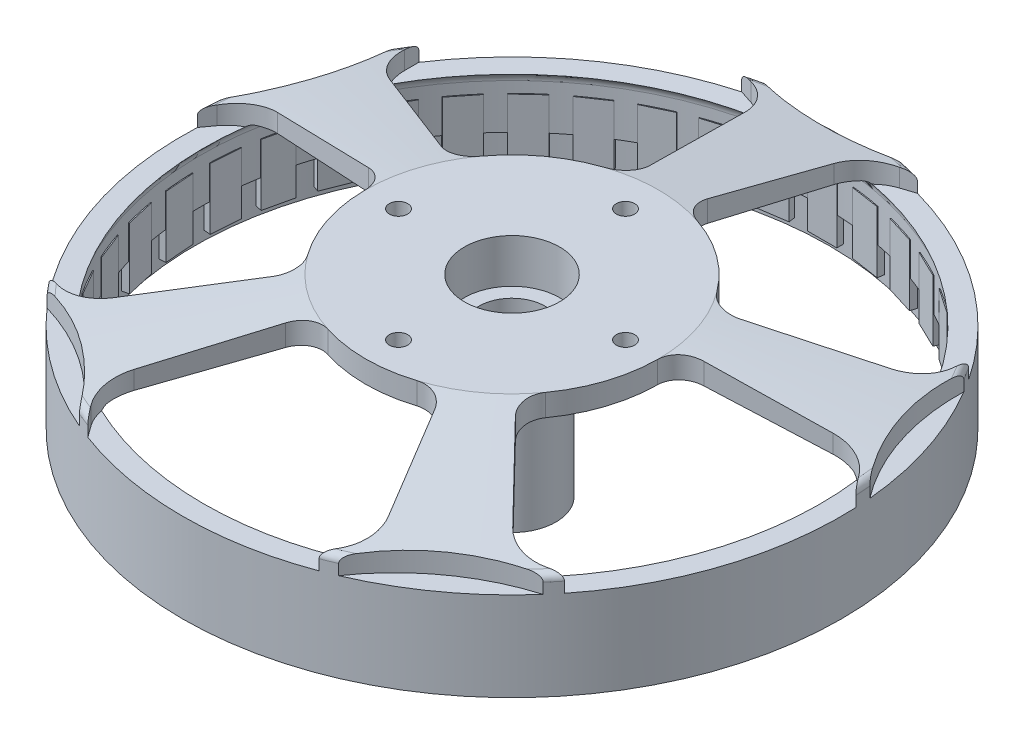
SolidWorks part; units mm, degrees
ref_plane "Front Plane" through (0, 0, 0) normal (0, 0, 1) x (1, 0, 0)
ref_plane "Top Plane" through (0, 0, 0) normal (0, 1, 0) x (1, 0, 0)
ref_plane "Right Plane" through (0, 0, 0) normal (1, 0, 0) x (0, 0, -1)
sketch "Sketch2" plane through (0, 0, 0) normal (0, 0, 1) x (1, 0, 0)
  line L0 (0, 0) -> (0, -18.25) construction
  line L1 (0, -18.25) -> (45, -18.25) construction
  line L2 (45, -18.25) -> (45, -6.1)
  line L3 (20, -3) -> (8.5, -3)
  line L4 (42.5, -5.8) -> (42.5, -13.25)
  line L5 (42.5, -13.25) -> (43.3, -13.25)
  line L6 (43.3, -13.25) -> (43.3, -18.25)
  line L7 (43.3, -18.25) -> (45, -18.25)
  line L8 (20, 0) -> (6.5, 0)
  line L9 (20, 0) -> (45, -3.8)
  line L10 (45, -3.8) -> (45, -6.1)
  line L12 (8.5, -3) -> (8.5, -8)
  line L13 (20, -3) -> (42.5, -5.8)
  line L14 (8.5, -8) -> (6, -8)
  line L15 (6, -8) -> (6, -26.3)
  line L16 (6, -26.3) -> (4, -26.3)
  line L17 (4, -26.3) -> (4, -19.5)
  line L18 (4, -19.5) -> (4.5, -19.5)
  line L19 (4.5, -19.5) -> (4.5, -6)
  line L20 (4.5, -6) -> (6.5, -6)
  line L21 (6.5, -6) -> (6.5, 0)
  dimension "D1" = 18.25
  dimension "D2" = 45
  dimension "D3" = 12.15
  dimension "D4" = 1.7
  dimension "D5" = 5
  dimension "D6" = 2.5
  dimension "D7" = 3
  dimension "D8" = 2.3
  dimension "D9" = 20
  dimension "D10" = 2
  dimension "D11" = 26.3
  dimension "D12" = 6
  dimension "D13" = 4
  dimension "D14" = 4.5
  dimension "D15" = 6.5
  dimension "D16" = 8.5
  dimension "D17" = 6
  dimension "D18" = 5
  dimension "D19" = 19.5
revolve "Revolve1" add sketch "Sketch2" angle 360 about L0
fillet "Fillet1" radius 1 1 edges at (0, -3.8, 45)
fillet "Fillet2" radius 1.5 1 edges at (0, -5.8, 42.5)
fillet "Fillet3" radius 0.5 1 edges at (0, -19.5, 4.5)
sketch "Sketch3" plane through (0, 0, 0) normal (0, 1, 0) x (1, 0, 0)
  line L0 (0, 0) -> (0, -45) construction
  line L1 (0, 0) -> (-26.4503, -36.4058) construction
  line L2 (0, 0) -> (-42.7975, -13.9058) construction
  line L3 (0, 0) -> (-42.7975, 13.9058) construction
  line L4 (0, 0) -> (-26.4503, 36.4058) construction
  line L5 (0, 0) -> (0, 45) construction
  line L6 (0, 0) -> (26.4503, 36.4058) construction
  line L7 (0, 0) -> (42.7975, 13.9058) construction
  line L8 (0, 0) -> (42.7975, -13.9058) construction
  line L9 (0, 0) -> (26.4503, -36.4058) construction
  line L10 (7, 44.4522) -> (3.5, 19.6914) construction
  line L11 (17.646, 9.4137) -> (40.1135, 20.3939) construction
  line L12 (3.9384, 22.793) -> (6.0748, 37.9066)
  line L13 (20.4604, 10.7891) -> (34.1741, 17.4912)
  line L14 (10.1616, 42.7732) -> (12, 43.3705)
  line L15 (37.5396, 22.8819) -> (37.5396, 24.8149)
  line L16 (22.8945, 3.2978) -> (37.9285, 5.9363)
  line L17 (16.5837, -16.125) -> (27.1955, -27.0964)
  line L18 (43.8198, 3.5534) -> (44.956, 1.9895)
  line L19 (33.3623, -28.6314) -> (35.2007, -28.034)
  line L20 (10.2112, -20.7549) -> (17.3664, -34.2377)
  line L21 (-10.2112, -20.7549) -> (-17.3664, -34.2377)
  line L22 (16.9205, -40.5771) -> (15.7843, -42.1409)
  line L23 (-16.9205, -40.5771) -> (-15.7843, -42.1409)
  line L24 (-16.5837, -16.125) -> (-27.1955, -27.0964)
  line L25 (-22.8945, 3.2978) -> (-37.9285, 5.9363)
  line L26 (-33.3623, -28.6314) -> (-35.2007, -28.034)
  line L27 (-43.8198, 3.5534) -> (-44.956, 1.9895)
  line L28 (-20.4604, 10.7891) -> (-34.1741, 17.4912)
  line L29 (-3.9384, 22.793) -> (-6.0748, 37.9066)
  line L30 (-37.5396, 22.8819) -> (-37.5396, 24.8149)
  line L31 (-10.1616, 42.7732) -> (-12, 43.3705)
  circle A0 centre (0, 0) radius 45 construction
  arc A1 (3.5, 19.6914) -> (17.646, 9.4137) centre (0, 0) cw construction
  arc A3 (7, 44.4522) -> (40.1135, 20.3939) centre (0, 0) cw construction
  arc A4 (6.3013, 18.9814) -> (16.1052, 11.8584) centre (0, 0) cw
  arc A5 (6.3013, 18.9814) -> (3.9384, 22.793) centre (7.404, 22.3032) cw
  arc A6 (16.1052, 11.8584) -> (20.4604, 10.7891) centre (18.9236, 13.9337) ccw
  arc A7 (6.0748, 37.9066) -> (10.1616, 42.7732) centre (12.0157, 37.0668) cw
  arc A8 (34.1741, 17.4912) -> (37.5396, 22.8819) centre (31.5396, 22.8819) ccw
  arc A9 (12, 43.3705) -> (37.5396, 24.8149) centre (0, 0) cw
  arc A10 (19.9996, -0.1273) -> (16.2548, -11.6525) centre (0, 0) cw
  arc A11 (16.2548, -11.6525) -> (16.5837, -16.125) centre (19.0994, -13.6917) ccw
  arc A12 (37.9285, 5.9363) -> (43.8198, 3.5534) centre (38.9657, 0.0267) cw
  arc A13 (27.1955, -27.0964) -> (33.3623, -28.6314) centre (31.5082, -22.925) ccw
  arc A14 (44.956, 1.9895) -> (35.2007, -28.034) centre (0, 0) cw
  arc A15 (19.9996, -0.1273) -> (22.8945, 3.2978) centre (23.4995, -0.1495) cw
  arc A16 (6.0592, -19.0601) -> (-6.0592, -19.0601) centre (0, 0) cw
  arc A17 (-6.0592, -19.0601) -> (-10.2112, -20.7549) centre (-7.1195, -22.3956) ccw
  arc A18 (17.3664, -34.2377) -> (16.9205, -40.5771) centre (12.0664, -37.0503) cw
  arc A19 (-17.3664, -34.2377) -> (-16.9205, -40.5771) centre (-12.0664, -37.0503) ccw
  arc A20 (15.7843, -42.1409) -> (-15.7843, -42.1409) centre (0, 0) cw
  arc A21 (6.0592, -19.0601) -> (10.2112, -20.7549) centre (7.1195, -22.3956) cw
  arc A22 (-16.2548, -11.6525) -> (-19.9996, -0.1273) centre (0, 0) cw
  arc A23 (-19.9996, -0.1273) -> (-22.8945, 3.2978) centre (-23.4995, -0.1495) ccw
  arc A24 (-27.1955, -27.0964) -> (-33.3623, -28.6314) centre (-31.5082, -22.925) cw
  arc A25 (-37.9285, 5.9363) -> (-43.8198, 3.5534) centre (-38.9657, 0.0267) ccw
  arc A26 (-35.2007, -28.034) -> (-44.956, 1.9895) centre (0, 0) cw
  arc A27 (-16.2548, -11.6525) -> (-16.5837, -16.125) centre (-19.0994, -13.6917) cw
  arc A28 (-16.1052, 11.8584) -> (-6.3013, 18.9814) centre (0, 0) cw
  arc A29 (-6.3013, 18.9814) -> (-3.9384, 22.793) centre (-7.404, 22.3032) ccw
  arc A30 (-34.1741, 17.4912) -> (-37.5396, 22.8819) centre (-31.5396, 22.8819) cw
  arc A31 (-6.0748, 37.9066) -> (-10.1616, 42.7732) centre (-12.0157, 37.0668) ccw
  arc A32 (-37.5396, 24.8149) -> (-12, 43.3705) centre (0, 0) cw
  arc A33 (-16.1052, 11.8584) -> (-20.4604, 10.7891) centre (-18.9236, 13.9337) cw
  circle A34 centre (0, 0) radius 20 construction
  point P17 (0, 0)
  point P95 (0, 0)
  dimension "D4" = 3.5
  dimension "D5" = 6
  dimension "D2" = 3.5
  dimension "D3" = 7
  dimension "D6" = 12
  dimension "D1" = 10
  dimension "D7" = 5
extrude "Cut-Extrude2" cut sketch "Sketch3" against normal offset from surface (6.1 mm away) 12.15 up to face at (0, -18.25, 45)
sketch "Sketch4" plane through (0, 0, 0) normal (0, 1, 0) x (1, 0, 0)
  line L0 (0, 0) -> (0, 72.1591) construction
  line L1 (-10, 43.8748) -> (10, 43.8748) construction
  line L2 (0, 0) -> (68.6274, 22.2984) construction
  line L3 (0, 0) -> (42.4141, -58.3779) construction
  line L4 (0, 0) -> (-42.4141, -58.3779) construction
  line L5 (0, 0) -> (-68.6274, 22.2984) construction
  circle A0 centre (0, 72.1591) radius 30
  arc A1 (-35.2007, 28.034) -> (-12, 43.3705) centre (0, 0) ccw construction
  circle A2 centre (68.6274, 22.2984) radius 30
  circle A3 centre (42.4141, -58.3779) radius 30
  circle A4 centre (-42.4141, -58.3779) radius 30
  circle A5 centre (-68.6274, 22.2984) radius 30
  point P20 (0, 0)
  dimension "D1" = 60
  dimension "D2" = 20
  dimension "D3" = 5
extrude "Cut-Extrude3" cut sketch "Sketch4" against normal offset from surface (6.1 mm away) 12.15 up to face at (0, -18.25, 45)
sketch "Sketch6" plane through (0, -13.25, 0) normal (0, -1, 0) x (1, 0, 0)
  line L0 (0, 0) -> (0, -42.8038) construction
  line L1 (-4.3348, -42.1788) -> (-8.2902, -41.5826)
  line L2 (2, -42.3538) -> (-2, -42.3538)
  line L3 (2, -42.3538) -> (2, -43.2538)
  line L4 (2, -43.2538) -> (-2, -43.2538) construction
  line L5 (-2, -42.3538) -> (-2, -43.2538)
  line L6 (2, -42.3538) -> (-2, -43.2538) construction
  line L7 (2, -43.2538) -> (-2, -42.3538) construction
  line L8 (-4.3348, -42.1788) -> (-4.469, -43.0688)
  line L9 (-8.2902, -41.5826) -> (-8.4243, -42.4726)
  line L10 (-4.469, -43.0688) -> (-8.4243, -42.4726) construction
  line L11 (-4.3348, -42.1788) -> (-8.4243, -42.4726) construction
  line L12 (-4.469, -43.0688) -> (-8.2902, -41.5826) construction
  line L13 (-10.5729, -41.0616) -> (-14.3951, -39.8826)
  line L14 (-10.5729, -41.0616) -> (-10.8381, -41.9217)
  line L15 (-14.3951, -39.8826) -> (-14.6604, -40.7426)
  line L16 (-10.8381, -41.9217) -> (-14.6604, -40.7426) construction
  line L17 (-10.5729, -41.0616) -> (-14.6604, -40.7426) construction
  line L18 (-10.8381, -41.9217) -> (-14.3951, -39.8826) construction
  line L19 (-16.5747, -39.0272) -> (-20.1786, -37.2917)
  line L20 (-16.5747, -39.0272) -> (-16.9652, -39.8381)
  line L21 (-20.1786, -37.2917) -> (-20.5691, -38.1025)
  line L22 (-16.9652, -39.8381) -> (-20.5691, -38.1025) construction
  line L23 (-16.5747, -39.0272) -> (-20.5691, -38.1025) construction
  line L24 (-16.9652, -39.8381) -> (-20.1786, -37.2917) construction
  line L25 (-22.2063, -36.121) -> (-25.5112, -33.8677)
  line L26 (-22.2063, -36.121) -> (-22.7132, -36.8646)
  line L27 (-25.5112, -33.8677) -> (-26.0182, -34.6113)
  line L28 (-22.7132, -36.8646) -> (-26.0182, -34.6113) construction
  line L29 (-22.2063, -36.121) -> (-26.0182, -34.6113) construction
  line L30 (-22.7132, -36.8646) -> (-25.5112, -33.8677) construction
  line L31 (-27.3418, -32.4079) -> (-30.274, -29.6872)
  line L32 (-27.3418, -32.4079) -> (-27.9539, -33.0676)
  line L33 (-30.274, -29.6872) -> (-30.8861, -30.3469)
  line L34 (-27.9539, -33.0676) -> (-30.8861, -30.3469) construction
  line L35 (-27.3418, -32.4079) -> (-30.8861, -30.3469) construction
  line L36 (-27.9539, -33.0676) -> (-30.274, -29.6872) construction
  line L37 (-31.8665, -27.9708) -> (-34.3605, -24.8435)
  line L38 (-31.8665, -27.9708) -> (-32.5702, -28.532)
  line L39 (-34.3605, -24.8435) -> (-35.0642, -25.4046)
  line L40 (-32.5702, -28.532) -> (-35.0642, -25.4046) construction
  line L41 (-31.8665, -27.9708) -> (-35.0642, -25.4046) construction
  line L42 (-32.5702, -28.532) -> (-34.3605, -24.8435) construction
  line L43 (-35.6795, -22.9089) -> (-37.6795, -19.4448)
  line L44 (-35.6795, -22.9089) -> (-36.4589, -23.3589)
  line L45 (-37.6795, -19.4448) -> (-38.4589, -19.8948)
  line L46 (-36.4589, -23.3589) -> (-38.4589, -19.8948) construction
  line L47 (-35.6795, -22.9089) -> (-38.4589, -19.8948) construction
  line L48 (-36.4589, -23.3589) -> (-37.6795, -19.4448) construction
  line L49 (-38.6953, -17.3353) -> (-40.1567, -13.6118)
  line L50 (-38.6953, -17.3353) -> (-39.5331, -17.6641)
  line L51 (-40.1567, -13.6118) -> (-40.9945, -13.9406)
  line L52 (-39.5331, -17.6641) -> (-40.9945, -13.9406) construction
  line L53 (-38.6953, -17.3353) -> (-40.9945, -13.9406) construction
  line L54 (-39.5331, -17.6641) -> (-40.1567, -13.6118) construction
  line L55 (-40.8468, -11.3745) -> (-41.7369, -7.4747)
  line L56 (-40.8468, -11.3745) -> (-41.7243, -11.5747)
  line L57 (-41.7369, -7.4747) -> (-42.6144, -7.675)
  line L58 (-41.7243, -11.5747) -> (-42.6144, -7.675) construction
  line L59 (-40.8468, -11.3745) -> (-42.6144, -7.675) construction
  line L60 (-41.7243, -11.5747) -> (-41.7369, -7.4747) construction
  line L61 (-42.0859, -5.1595) -> (-42.3848, -1.1707)
  line L62 (-42.0859, -5.1595) -> (-42.9834, -5.2268)
  line L63 (-42.3848, -1.1707) -> (-43.2823, -1.238)
  line L64 (-42.9834, -5.2268) -> (-43.2823, -1.238) construction
  line L65 (-42.0859, -5.1595) -> (-43.2823, -1.238) construction
  line L66 (-42.9834, -5.2268) -> (-42.3848, -1.1707) construction
  line L67 (-42.3848, 1.1707) -> (-42.0859, 5.1595)
  line L68 (-42.3848, 1.1707) -> (-43.2823, 1.238)
  line L69 (-42.0859, 5.1595) -> (-42.9834, 5.2268)
  line L70 (-43.2823, 1.238) -> (-42.9834, 5.2268) construction
  line L71 (-42.3848, 1.1707) -> (-42.9834, 5.2268) construction
  line L72 (-43.2823, 1.238) -> (-42.0859, 5.1595) construction
  line L73 (-41.7369, 7.4747) -> (-40.8468, 11.3745)
  line L74 (-41.7369, 7.4747) -> (-42.6144, 7.675)
  line L75 (-40.8468, 11.3745) -> (-41.7243, 11.5747)
  line L76 (-42.6144, 7.675) -> (-41.7243, 11.5747) construction
  line L77 (-41.7369, 7.4747) -> (-41.7243, 11.5747) construction
  line L78 (-42.6144, 7.675) -> (-40.8468, 11.3745) construction
  line L79 (-40.1567, 13.6118) -> (-38.6953, 17.3353)
  line L80 (-40.1567, 13.6118) -> (-40.9945, 13.9406)
  line L81 (-38.6953, 17.3353) -> (-39.5331, 17.6641)
  line L82 (-40.9945, 13.9406) -> (-39.5331, 17.6641) construction
  line L83 (-40.1567, 13.6118) -> (-39.5331, 17.6641) construction
  line L84 (-40.9945, 13.9406) -> (-38.6953, 17.3353) construction
  line L85 (-37.6795, 19.4448) -> (-35.6795, 22.9089)
  line L86 (-37.6795, 19.4448) -> (-38.4589, 19.8948)
  line L87 (-35.6795, 22.9089) -> (-36.4589, 23.3589)
  line L88 (-38.4589, 19.8948) -> (-36.4589, 23.3589) construction
  line L89 (-37.6795, 19.4448) -> (-36.4589, 23.3589) construction
  line L90 (-38.4589, 19.8948) -> (-35.6795, 22.9089) construction
  line L91 (-34.3605, 24.8435) -> (-31.8665, 27.9708)
  line L92 (-34.3605, 24.8435) -> (-35.0642, 25.4046)
  line L93 (-31.8665, 27.9708) -> (-32.5702, 28.532)
  line L94 (-35.0642, 25.4046) -> (-32.5702, 28.532) construction
  line L95 (-34.3605, 24.8435) -> (-32.5702, 28.532) construction
  line L96 (-35.0642, 25.4046) -> (-31.8665, 27.9708) construction
  line L97 (-30.274, 29.6872) -> (-27.3418, 32.4079)
  line L98 (-30.274, 29.6872) -> (-30.8861, 30.3469)
  line L99 (-27.3418, 32.4079) -> (-27.9539, 33.0676)
  line L100 (-30.8861, 30.3469) -> (-27.9539, 33.0676) construction
  line L101 (-30.274, 29.6872) -> (-27.9539, 33.0676) construction
  line L102 (-30.8861, 30.3469) -> (-27.3418, 32.4079) construction
  line L103 (-25.5112, 33.8677) -> (-22.2063, 36.121)
  line L104 (-25.5112, 33.8677) -> (-26.0182, 34.6113)
  line L105 (-22.2063, 36.121) -> (-22.7132, 36.8646)
  line L106 (-26.0182, 34.6113) -> (-22.7132, 36.8646) construction
  line L107 (-25.5112, 33.8677) -> (-22.7132, 36.8646) construction
  line L108 (-26.0182, 34.6113) -> (-22.2063, 36.121) construction
  line L109 (-20.1786, 37.2917) -> (-16.5747, 39.0272)
  line L110 (-20.1786, 37.2917) -> (-20.5691, 38.1025)
  line L111 (-16.5747, 39.0272) -> (-16.9652, 39.8381)
  line L112 (-20.5691, 38.1025) -> (-16.9652, 39.8381) construction
  line L113 (-20.1786, 37.2917) -> (-16.9652, 39.8381) construction
  line L114 (-20.5691, 38.1025) -> (-16.5747, 39.0272) construction
  line L115 (-14.3951, 39.8826) -> (-10.5729, 41.0616)
  line L116 (-14.3951, 39.8826) -> (-14.6604, 40.7426)
  line L117 (-10.5729, 41.0616) -> (-10.8381, 41.9217)
  line L118 (-14.6604, 40.7426) -> (-10.8381, 41.9217) construction
  line L119 (-14.3951, 39.8826) -> (-10.8381, 41.9217) construction
  line L120 (-14.6604, 40.7426) -> (-10.5729, 41.0616) construction
  line L121 (-8.2902, 41.5826) -> (-4.3348, 42.1788)
  line L122 (-8.2902, 41.5826) -> (-8.4243, 42.4726)
  line L123 (-4.3348, 42.1788) -> (-4.469, 43.0688)
  line L124 (-8.4243, 42.4726) -> (-4.469, 43.0688) construction
  line L125 (-8.2902, 41.5826) -> (-4.469, 43.0688) construction
  line L126 (-8.4243, 42.4726) -> (-4.3348, 42.1788) construction
  line L127 (-2, 42.3538) -> (2, 42.3538)
  line L128 (-2, 42.3538) -> (-2, 43.2538)
  line L129 (2, 42.3538) -> (2, 43.2538)
  line L130 (-2, 43.2538) -> (2, 43.2538) construction
  line L131 (-2, 42.3538) -> (2, 43.2538) construction
  line L132 (-2, 43.2538) -> (2, 42.3538) construction
  line L133 (4.3348, 42.1788) -> (8.2902, 41.5826)
  line L134 (4.3348, 42.1788) -> (4.469, 43.0688)
  line L135 (8.2902, 41.5826) -> (8.4243, 42.4726)
  line L136 (4.469, 43.0688) -> (8.4243, 42.4726) construction
  line L137 (4.3348, 42.1788) -> (8.4243, 42.4726) construction
  line L138 (4.469, 43.0688) -> (8.2902, 41.5826) construction
  line L139 (10.5729, 41.0616) -> (14.3951, 39.8826)
  line L140 (10.5729, 41.0616) -> (10.8381, 41.9217)
  line L141 (14.3951, 39.8826) -> (14.6604, 40.7426)
  line L142 (10.8381, 41.9217) -> (14.6604, 40.7426) construction
  line L143 (10.5729, 41.0616) -> (14.6604, 40.7426) construction
  line L144 (10.8381, 41.9217) -> (14.3951, 39.8826) construction
  line L145 (16.5747, 39.0272) -> (20.1786, 37.2917)
  line L146 (16.5747, 39.0272) -> (16.9652, 39.8381)
  line L147 (20.1786, 37.2917) -> (20.5691, 38.1025)
  line L148 (16.9652, 39.8381) -> (20.5691, 38.1025) construction
  line L149 (16.5747, 39.0272) -> (20.5691, 38.1025) construction
  line L150 (16.9652, 39.8381) -> (20.1786, 37.2917) construction
  line L151 (22.2063, 36.121) -> (25.5112, 33.8677)
  line L152 (22.2063, 36.121) -> (22.7132, 36.8646)
  line L153 (25.5112, 33.8677) -> (26.0182, 34.6113)
  line L154 (22.7132, 36.8646) -> (26.0182, 34.6113) construction
  line L155 (22.2063, 36.121) -> (26.0182, 34.6113) construction
  line L156 (22.7132, 36.8646) -> (25.5112, 33.8677) construction
  line L157 (27.3418, 32.4079) -> (30.274, 29.6872)
  line L158 (27.3418, 32.4079) -> (27.9539, 33.0676)
  line L159 (30.274, 29.6872) -> (30.8861, 30.3469)
  line L160 (27.9539, 33.0676) -> (30.8861, 30.3469) construction
  line L161 (27.3418, 32.4079) -> (30.8861, 30.3469) construction
  line L162 (27.9539, 33.0676) -> (30.274, 29.6872) construction
  line L163 (31.8665, 27.9708) -> (34.3605, 24.8435)
  line L164 (31.8665, 27.9708) -> (32.5702, 28.532)
  line L165 (34.3605, 24.8435) -> (35.0642, 25.4046)
  line L166 (32.5702, 28.532) -> (35.0642, 25.4046) construction
  line L167 (31.8665, 27.9708) -> (35.0642, 25.4046) construction
  line L168 (32.5702, 28.532) -> (34.3605, 24.8435) construction
  line L169 (35.6795, 22.9089) -> (37.6795, 19.4448)
  line L170 (35.6795, 22.9089) -> (36.4589, 23.3589)
  line L171 (37.6795, 19.4448) -> (38.4589, 19.8948)
  line L172 (36.4589, 23.3589) -> (38.4589, 19.8948) construction
  line L173 (35.6795, 22.9089) -> (38.4589, 19.8948) construction
  line L174 (36.4589, 23.3589) -> (37.6795, 19.4448) construction
  line L175 (38.6953, 17.3353) -> (40.1567, 13.6118)
  line L176 (38.6953, 17.3353) -> (39.5331, 17.6641)
  line L177 (40.1567, 13.6118) -> (40.9945, 13.9406)
  line L178 (39.5331, 17.6641) -> (40.9945, 13.9406) construction
  line L179 (38.6953, 17.3353) -> (40.9945, 13.9406) construction
  line L180 (39.5331, 17.6641) -> (40.1567, 13.6118) construction
  line L181 (40.8468, 11.3745) -> (41.7369, 7.4747)
  line L182 (40.8468, 11.3745) -> (41.7243, 11.5747)
  line L183 (41.7369, 7.4747) -> (42.6144, 7.675)
  line L184 (41.7243, 11.5747) -> (42.6144, 7.675) construction
  line L185 (40.8468, 11.3745) -> (42.6144, 7.675) construction
  line L186 (41.7243, 11.5747) -> (41.7369, 7.4747) construction
  line L187 (42.0859, 5.1595) -> (42.3848, 1.1707)
  line L188 (42.0859, 5.1595) -> (42.9834, 5.2268)
  line L189 (42.3848, 1.1707) -> (43.2823, 1.238)
  line L190 (42.9834, 5.2268) -> (43.2823, 1.238) construction
  line L191 (42.0859, 5.1595) -> (43.2823, 1.238) construction
  line L192 (42.9834, 5.2268) -> (42.3848, 1.1707) construction
  line L193 (42.3848, -1.1707) -> (42.0859, -5.1595)
  line L194 (42.3848, -1.1707) -> (43.2823, -1.238)
  line L195 (42.0859, -5.1595) -> (42.9834, -5.2268)
  line L196 (43.2823, -1.238) -> (42.9834, -5.2268) construction
  line L197 (42.3848, -1.1707) -> (42.9834, -5.2268) construction
  line L198 (43.2823, -1.238) -> (42.0859, -5.1595) construction
  line L199 (41.7369, -7.4747) -> (40.8468, -11.3745)
  line L200 (41.7369, -7.4747) -> (42.6144, -7.675)
  line L201 (40.8468, -11.3745) -> (41.7243, -11.5747)
  line L202 (42.6144, -7.675) -> (41.7243, -11.5747) construction
  line L203 (41.7369, -7.4747) -> (41.7243, -11.5747) construction
  line L204 (42.6144, -7.675) -> (40.8468, -11.3745) construction
  line L205 (40.1567, -13.6118) -> (38.6953, -17.3353)
  line L206 (40.1567, -13.6118) -> (40.9945, -13.9406)
  line L207 (38.6953, -17.3353) -> (39.5331, -17.6641)
  line L208 (40.9945, -13.9406) -> (39.5331, -17.6641) construction
  line L209 (40.1567, -13.6118) -> (39.5331, -17.6641) construction
  line L210 (40.9945, -13.9406) -> (38.6953, -17.3353) construction
  line L211 (37.6795, -19.4448) -> (35.6795, -22.9089)
  line L212 (37.6795, -19.4448) -> (38.4589, -19.8948)
  line L213 (35.6795, -22.9089) -> (36.4589, -23.3589)
  line L214 (38.4589, -19.8948) -> (36.4589, -23.3589) construction
  line L215 (37.6795, -19.4448) -> (36.4589, -23.3589) construction
  line L216 (38.4589, -19.8948) -> (35.6795, -22.9089) construction
  line L217 (34.3605, -24.8435) -> (31.8665, -27.9708)
  line L218 (34.3605, -24.8435) -> (35.0642, -25.4046)
  line L219 (31.8665, -27.9708) -> (32.5702, -28.532)
  line L220 (35.0642, -25.4046) -> (32.5702, -28.532) construction
  line L221 (34.3605, -24.8435) -> (32.5702, -28.532) construction
  line L222 (35.0642, -25.4046) -> (31.8665, -27.9708) construction
  line L223 (30.274, -29.6872) -> (27.3418, -32.4079)
  line L224 (30.274, -29.6872) -> (30.8861, -30.3469)
  line L225 (27.3418, -32.4079) -> (27.9539, -33.0676)
  line L226 (30.8861, -30.3469) -> (27.9539, -33.0676) construction
  line L227 (30.274, -29.6872) -> (27.9539, -33.0676) construction
  line L228 (30.8861, -30.3469) -> (27.3418, -32.4079) construction
  line L229 (25.5112, -33.8677) -> (22.2063, -36.121)
  line L230 (25.5112, -33.8677) -> (26.0182, -34.6113)
  line L231 (22.2063, -36.121) -> (22.7132, -36.8646)
  line L232 (26.0182, -34.6113) -> (22.7132, -36.8646) construction
  line L233 (25.5112, -33.8677) -> (22.7132, -36.8646) construction
  line L234 (26.0182, -34.6113) -> (22.2063, -36.121) construction
  line L235 (20.1786, -37.2917) -> (16.5747, -39.0272)
  line L236 (20.1786, -37.2917) -> (20.5691, -38.1025)
  line L237 (16.5747, -39.0272) -> (16.9652, -39.8381)
  line L238 (20.5691, -38.1025) -> (16.9652, -39.8381) construction
  line L239 (20.1786, -37.2917) -> (16.9652, -39.8381) construction
  line L240 (20.5691, -38.1025) -> (16.5747, -39.0272) construction
  line L241 (14.3951, -39.8826) -> (10.5729, -41.0616)
  line L242 (14.3951, -39.8826) -> (14.6604, -40.7426)
  line L243 (10.5729, -41.0616) -> (10.8381, -41.9217)
  line L244 (14.6604, -40.7426) -> (10.8381, -41.9217) construction
  line L245 (14.3951, -39.8826) -> (10.8381, -41.9217) construction
  line L246 (14.6604, -40.7426) -> (10.5729, -41.0616) construction
  line L247 (8.2902, -41.5826) -> (4.3348, -42.1788)
  line L248 (8.2902, -41.5826) -> (8.4243, -42.4726)
  line L249 (4.3348, -42.1788) -> (4.469, -43.0688)
  line L250 (8.4243, -42.4726) -> (4.469, -43.0688) construction
  line L251 (8.2902, -41.5826) -> (4.469, -43.0688) construction
  line L252 (8.4243, -42.4726) -> (4.3348, -42.1788) construction
  arc A0 (2, -43.2538) -> (-2, -43.2538) centre (0, 0) cw
  circle A1 centre (0, 0) radius 43.3 construction
  arc A2 (-4.469, -43.0688) -> (-8.4243, -42.4726) centre (0, 0) cw
  arc A3 (-10.8381, -41.9217) -> (-14.6604, -40.7426) centre (0, 0) cw
  arc A4 (-16.9652, -39.8381) -> (-20.5691, -38.1025) centre (0, 0) cw
  arc A5 (-22.7132, -36.8646) -> (-26.0182, -34.6113) centre (0, 0) cw
  arc A6 (-27.9539, -33.0676) -> (-30.8861, -30.3469) centre (0, 0) cw
  arc A7 (-32.5702, -28.532) -> (-35.0642, -25.4046) centre (0, 0) cw
  arc A8 (-36.4589, -23.3589) -> (-38.4589, -19.8948) centre (0, 0) cw
  arc A9 (-39.5331, -17.6641) -> (-40.9945, -13.9406) centre (0, 0) cw
  arc A10 (-41.7243, -11.5747) -> (-42.6144, -7.675) centre (0, 0) cw
  arc A11 (-42.9834, -5.2268) -> (-43.2823, -1.238) centre (0, 0) cw
  arc A12 (-43.2823, 1.238) -> (-42.9834, 5.2268) centre (0, 0) cw
  arc A13 (-42.6144, 7.675) -> (-41.7243, 11.5747) centre (0, 0) cw
  arc A14 (-40.9945, 13.9406) -> (-39.5331, 17.6641) centre (0, 0) cw
  arc A15 (-38.4589, 19.8948) -> (-36.4589, 23.3589) centre (0, 0) cw
  arc A16 (-35.0642, 25.4046) -> (-32.5702, 28.532) centre (0, 0) cw
  arc A17 (-30.8861, 30.3469) -> (-27.9539, 33.0676) centre (0, 0) cw
  arc A18 (-26.0182, 34.6113) -> (-22.7132, 36.8646) centre (0, 0) cw
  arc A19 (-20.5691, 38.1025) -> (-16.9652, 39.8381) centre (0, 0) cw
  arc A20 (-14.6604, 40.7426) -> (-10.8381, 41.9217) centre (0, 0) cw
  arc A21 (-8.4243, 42.4726) -> (-4.469, 43.0688) centre (0, 0) cw
  arc A22 (-2, 43.2538) -> (2, 43.2538) centre (0, 0) cw
  arc A23 (4.469, 43.0688) -> (8.4243, 42.4726) centre (0, 0) cw
  arc A24 (10.8381, 41.9217) -> (14.6604, 40.7426) centre (0, 0) cw
  arc A25 (16.9652, 39.8381) -> (20.5691, 38.1025) centre (0, 0) cw
  arc A26 (22.7132, 36.8646) -> (26.0182, 34.6113) centre (0, 0) cw
  arc A27 (27.9539, 33.0676) -> (30.8861, 30.3469) centre (0, 0) cw
  arc A28 (32.5702, 28.532) -> (35.0642, 25.4046) centre (0, 0) cw
  arc A29 (36.4589, 23.3589) -> (38.4589, 19.8948) centre (0, 0) cw
  arc A30 (39.5331, 17.6641) -> (40.9945, 13.9406) centre (0, 0) cw
  arc A31 (41.7243, 11.5747) -> (42.6144, 7.675) centre (0, 0) cw
  arc A32 (42.9834, 5.2268) -> (43.2823, 1.238) centre (0, 0) cw
  arc A33 (43.2823, -1.238) -> (42.9834, -5.2268) centre (0, 0) cw
  arc A34 (42.6144, -7.675) -> (41.7243, -11.5747) centre (0, 0) cw
  arc A35 (40.9945, -13.9406) -> (39.5331, -17.6641) centre (0, 0) cw
  arc A36 (38.4589, -19.8948) -> (36.4589, -23.3589) centre (0, 0) cw
  arc A37 (35.0642, -25.4046) -> (32.5702, -28.532) centre (0, 0) cw
  arc A38 (30.8861, -30.3469) -> (27.9539, -33.0676) centre (0, 0) cw
  arc A39 (26.0182, -34.6113) -> (22.7132, -36.8646) centre (0, 0) cw
  arc A40 (20.5691, -38.1025) -> (16.9652, -39.8381) centre (0, 0) cw
  arc A41 (14.6604, -40.7426) -> (10.8381, -41.9217) centre (0, 0) cw
  arc A42 (8.4243, -42.4726) -> (4.469, -43.0688) centre (0, 0) cw
  point P177 (0, 0)
  dimension "D1" = 0.9
  dimension "D2" = 4
  dimension "D3" = 42
extrude "Boss-Extrude6" add sketch "Sketch6" along normal blind 3.8 and the other way blind 4.6
hole_wizard "Tap Drill for M3x0.5 Tap2" positions "Sketch12" profile "Sketch13" hole size "M3x0.5" standard "ANSI Metric" end condition through all
sketch "Sketch12" plane through (0, 0, 0) normal (0, 1, 0) x (1, 0, 0)
  point P0 (0, 15.5)
  point P6 (15.5, 0)
  point P7 (0, -15.5)
  point P8 (-15.5, 0)
  dimension "D2" = 15.5
  dimension "D1" = 4
sketch "Sketch13" plane through (0, 0, -15.5) normal (1, 0, 0) x (0, 0, 1)
  line L0 (0, 0) -> (0, 26.3)
  line L1 (0, 26.3) -> (1.25, 26.3)
  line L2 (1.25, 26.3) -> (1.25, 0)
  line L5 (1.25, 0) -> (0, 0)
  line L11 (0, -6.35) -> (0, 107.95) construction
  dimension "Thru Hole Dia." = 2.5
  dimension "Thru Hole Depth" = 26.3
